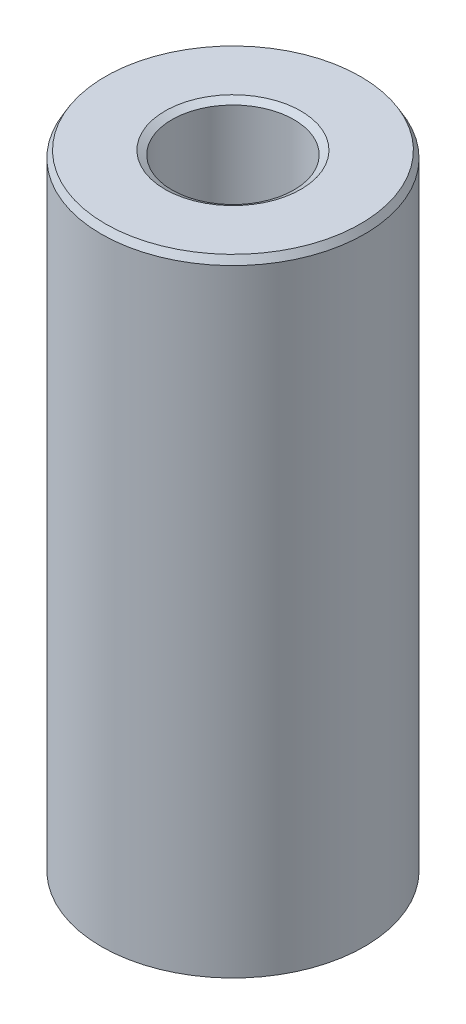
SolidWorks part; units mm, degrees
ref_plane "Front Plane" through (0, 0, 0) normal (0, 0, 1) x (1, 0, 0)
ref_plane "Top Plane" through (0, 0, 0) normal (0, 1, 0) x (1, 0, 0)
ref_plane "Right Plane" through (0, 0, 0) normal (1, 0, 0) x (0, 0, -1)
sketch "Sketch1" plane through (0, 0, 0) normal (0, 1, 0) x (1, 0, 0)
  circle A0 centre (0, 0) radius 42.5
  dimension "SLEEVE_OD" = 85
extrude "Boss-Extrude1" add sketch "Sketch1" along normal blind 202.766
sketch "Sketch2" plane through (0, 0, 0) normal (0, 1, 0) x (1, 0, 0)
  circle A0 centre (0, 0) radius 19.6984
  dimension "BORE_D" = 39.3967
extrude "Cut-Extrude1" cut sketch "Sketch2" along normal through all
chamfer "Chamfer1" distance 2.2371 angle 30 4 edges at (0, 202.766, 19.6984) (0, 0, 19.6984) (0, 0, 42.5) (0, 202.766, 42.5) first distance on face at (0, 202.766, 19.6984) first distance on face at (0, 0, 19.6984) first distance on face at (0, 202.766, 42.5)
